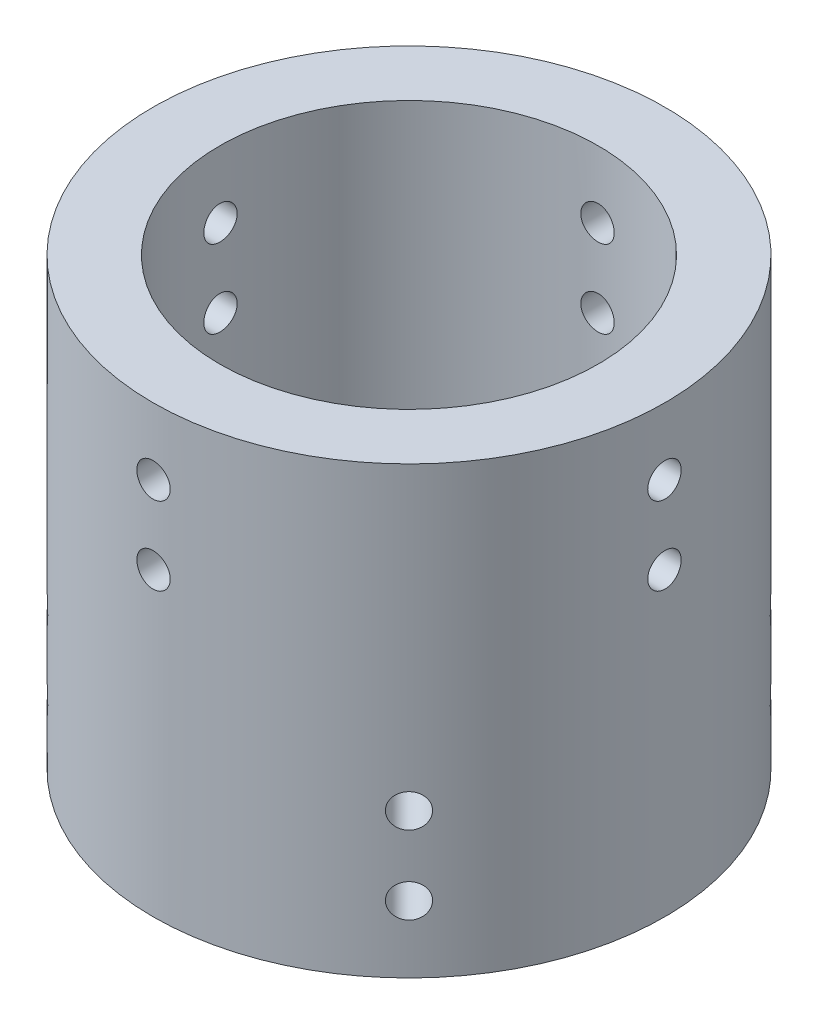
SolidWorks part; units mm, degrees
ref_plane "Спереди" through (0, 0, 0) normal (0, 0, 1) x (1, 0, 0)
ref_plane "Сверху" through (0, 0, 0) normal (0, 1, 0) x (1, 0, 0)
ref_plane "Справа" through (0, 0, 0) normal (1, 0, 0) x (0, 0, -1)
sketch "Эскиз1" plane through (0, 0, 0) normal (0, 1, 0) x (1, 0, 0)
  circle A0 centre (0, 0) radius 23
  dimension "D1" = 46
extrude "Бобышка-Вытянуть1" add sketch "Эскиз1" along normal blind 10
sketch "Эскиз2" plane through (0, 10, 0) normal (0, 1, 0) x (1, 0, 0)
  circle A0 centre (0, 0) radius 23
  circle A1 centre (0, 0) radius 17
  circle A2 centre (0, 0) radius 23 construction
  dimension "D1" = 34
  dimension "D2" = 0
extrude "Бобышка-Вытянуть2" add sketch "Эскиз2" along normal blind 30
sketch "Эскиз3" plane through (0, 0, 0) normal (1, 0, 0) x (0, 0, -1)
  line L0 (-23, 20) -> (30.2453, 20) construction
  line L1 (-23, 40) -> (-23, 0) construction
  line L2 (0, 27) -> (0, -3.082) construction
  circle A0 centre (0, 27) radius 1.5
  circle A1 centre (0, 34) radius 1.5
  dimension "D1" = 3
  dimension "D2" = 7
  dimension "D3" = 2
extrude "Вырез-Вытянуть1" cut sketch "Эскиз3" against normal through all
ref_plane "Плоскость1" through (0, 0, 0) normal (0.7071, 0, 0.7071) x (0, -1, 0)
sketch "Эскиз4" plane through (0, 0, 0) normal (0.7071, 0, 0.7071) x (0, -1, 0)
  line L0 (-20, 23) -> (-20, -29.9249) construction
  line L1 (0, 23) -> (-40, 23) construction
  line L2 (-40, 0) -> (0, 0) construction
  circle A0 centre (-13, 0) radius 1.5
  circle A1 centre (-6, 0) radius 1.5
  dimension "D1" = 3
  dimension "D2" = 7
  dimension "D3" = 2
extrude "Вырез-Вытянуть2" cut sketch "Эскиз4" against normal through all
pattern_circular "Круговой массив1" count 4 over 360 about axis through (0, 10, 0) along (0, -1, 0) of "Вырез-Вытянуть2", "Вырез-Вытянуть1"
